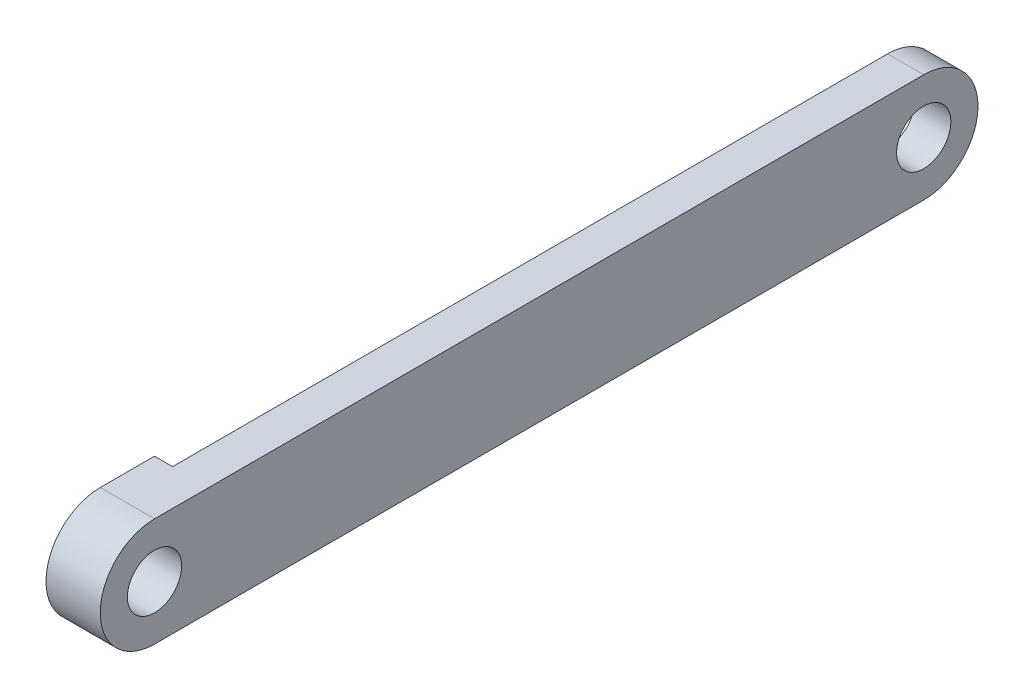
SolidWorks part; units mm, degrees
material "Plain Carbon Steel"
ref_plane "Front Plane" through (0, 0, 0) normal (0, 0, 1) x (1, 0, 0)
ref_plane "Top Plane" through (0, 0, 0) normal (0, 1, 0) x (1, 0, 0)
ref_plane "Right Plane" through (0, 0, 0) normal (1, 0, 0) x (0, 0, -1)
sketch "Sketch1" plane through (0, 0, 0) normal (1, 0, 0) x (0, 0, -1)
  line L24 (0, 3) -> (42.53, 3)
  line L25 (0, -3) -> (42.53, -3)
  arc A6 (0, 3) -> (0, -3) centre (0, 0) ccw
  arc A8 (42.53, 3) -> (42.53, -3) centre (42.53, 0) cw
  circle A10 centre (0, 0) radius 1.5
  circle A11 centre (42.53, 0) radius 1.5
  dimension "D1" = 6
  dimension "D2" = 42.53
  dimension "D3" = 3
extrude "Boss-Extrude1" add sketch "Sketch1" along normal blind 3
sketch "Sketch3" plane through (0, 0, 0) normal (-1, 0, 0) x (0, 0, 1)
  line L0 (-45.53, 3) -> (-3, 3)
  line L1 (-42.53, 3) -> (0, 3) construction
  line L2 (-3, 3) -> (-3, -3)
  line L3 (0, -3) -> (-42.53, -3) construction
  line L4 (-3, -3) -> (-45.53, -3)
  line L5 (-45.53, -3) -> (-45.53, 3)
  arc A0 (0, -3) -> (0, 3) centre (0, 0) ccw construction
  arc A1 (-42.53, 3) -> (-42.53, -3) centre (-42.53, 0) ccw construction
  point P14 (-3, 3)
  point P15 (-3, 3)
  point P16 (-52.45, 3.3012)
  dimension "D1" = 3
extrude "Cut-Extrude2" cut sketch "Sketch3" against normal blind 1
